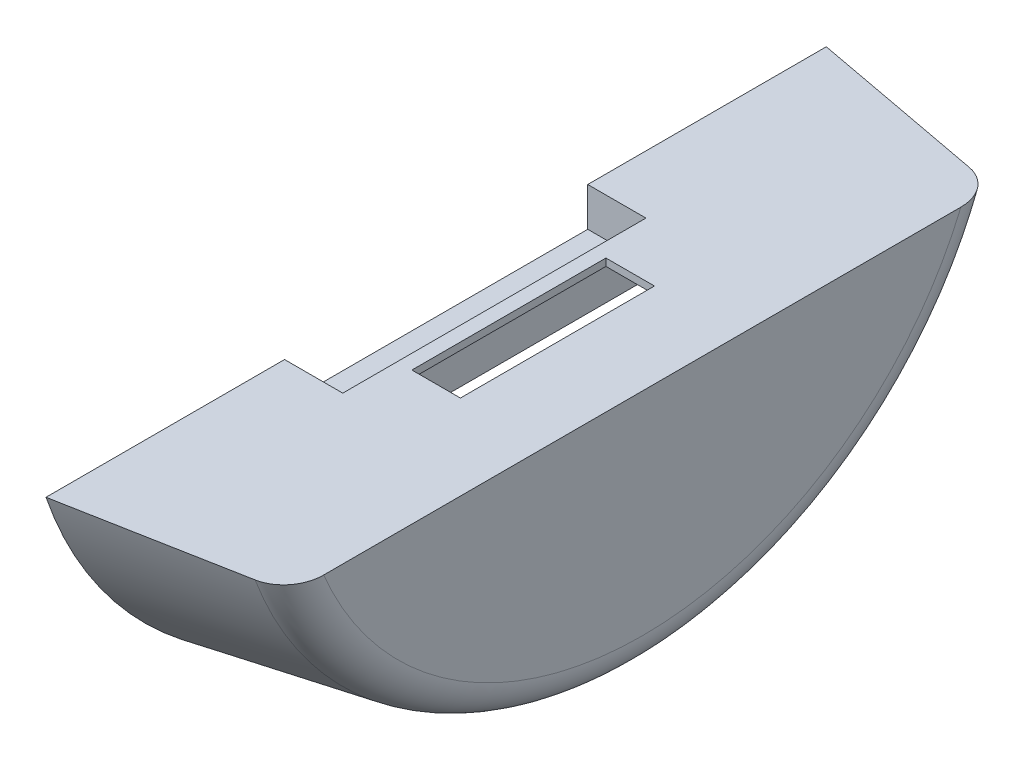
SolidWorks part; units mm, degrees
material "ABS"
ref_plane "Front Plane" through (0, 0, 0) normal (0, 0, 1) x (1, 0, 0)
ref_plane "Top Plane" through (0, 0, 0) normal (0, 1, 0) x (1, 0, 0)
ref_plane "Right Plane" through (0, 0, 0) normal (1, 0, 0) x (0, 0, -1)
sketch "Sketch1" plane through (0, 0, 0) normal (1, 0, 0) x (0, 0, -1)
  line L0 (-160.8571, -55) -> (160.8571, -55)
  arc A0 (-160.8571, -55) -> (160.8571, -55) centre (0, 0) ccw
  dimension "D1" = 340
  dimension "D2" = 55
extrude "Boss-Extrude1" add sketch "Sketch1" along normal blind 85
chamfer "Chamfer1" distance 85 distance2 15 1 edges at (85, -170, 0) first distance on face at (42.5, -112.5, 0)
sketch "Sketch3" plane through (0, -55, 0) normal (0, 1, 0) x (1, 0, 0)
  line L0 (0, 160.8571) -> (0, -160.8571) construction
  line L1 (0, 62.5) -> (24, 62.5)
  line L2 (0, 62.5) -> (0, -62.5)
  line L3 (0, -62.5) -> (24, -62.5)
  line L4 (24, 62.5) -> (24, -62.5)
  point P6 (24, 0)
  dimension "D1" = 24
  dimension "D2" = 125
extrude "Cut-Extrude2" cut sketch "Sketch3" against normal blind 16
fillet "Fillet2" radius 15 1 edges at (85, -155, 0)
shell "Shell1" thickness 3 removed face at (0, -79.5, 0)
sketch "Sketch2" plane through (0, -55, 0) normal (0, 1, 0) x (1, 0, 0)
  line L1 (30, 40) -> (50, 40)
  line L2 (30, 40) -> (30, -40)
  line L3 (30, -40) -> (50, -40)
  line L4 (50, 40) -> (50, -40)
  point P4 (30, 0)
  dimension "D1" = 80
  dimension "D2" = 20
  dimension "D3" = 30
extrude "Cut-Extrude1" cut sketch "Sketch2" against normal blind 10
